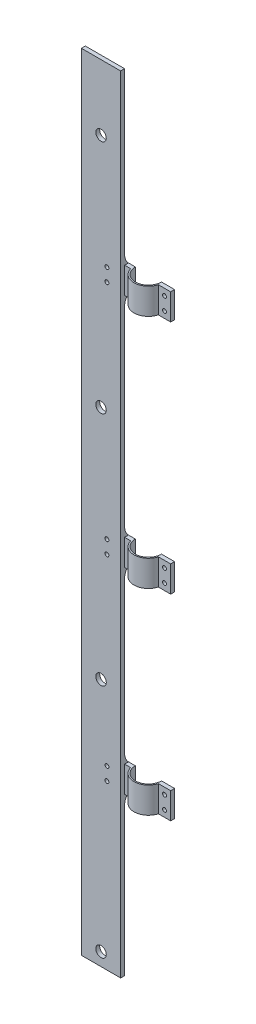
SolidWorks part; units mm, degrees
ref_plane "前视基准面" through (0, 0, 0) normal (0, 0, 1) x (1, 0, 0)
ref_plane "上视基准面" through (0, 0, 0) normal (0, 1, 0) x (1, 0, 0)
ref_plane "右视基准面" through (0, 0, 0) normal (1, 0, 0) x (0, 0, -1)
sketch "草图1" plane through (0, 0, 0) normal (0, 0, 1) x (1, 0, 0)
  line L0 (0, 0) -> (-30, 0)
  line L8 (-30, -300) -> (0, -300)
  line L9 (0, -300) -> (0, 300)
  line L10 (0, 300) -> (-30, 300)
  line L11 (-30, 300) -> (-30, -300)
  circle A6 centre (-15, 249.9934) radius 4
  circle A8 centre (-15, -290.0066) radius 4
  circle A10 centre (-15, -110.0066) radius 4
  circle A12 centre (-15, 69.9934) radius 4
extrude "凸台-拉伸1" add sketch "草图1" along normal blind 3 contours L10 L11 L0 L9 A12 A6 | L0 L11 L8 L9 A10 A8 region at (-15, -149.4351, 0) region at (-15, 149.8871, 0)
sketch "草图3" plane through (0, 0, 0) normal (0, 0, -1) x (-1, 0, 0)
  line L0 (15, 249.9934) -> (15, 159.9934)
  line L1 (15, 69.9934) -> (15, -20.0066)
  line L2 (15, -110.0066) -> (15, -170.0066)
ref_plane "基准面1" through (0, -20.0066, 0) normal (0, 1, 0) x (1, 0, 0)
ref_plane "基准面2" through (0, -170.0066, 0) normal (0, 1, 0) x (1, 0, 0)
ref_plane "基准面3" through (0, 159.9934, 0) normal (0, 1, 0) x (1, 0, 0)
sketch "草图10" plane through (0, -20.0066, 0) normal (0, 1, 0) x (1, 0, 0)
  line L0 (-30, 0) -> (4.617, 0)
  line L1 (-30, 3) -> (5.2, 3)
  line L2 (-30, 3) -> (-30, 0)
  line L4 (35.2, 3) -> (35.2, 0)
  line L7 (35.2, 0) -> (25.783, 0)
  line L10 (25.2, 3) -> (35.2, 3)
  arc A2 (25.783, 0) -> (4.617, 0) centre (15.2, 3) cw
  arc A3 (25.2, 3) -> (5.2, 3) centre (15.2, 3) cw
extrude "凸台-拉伸2" add sketch "草图10" along normal mid plane 20
sketch "草图11" plane through (0, 159.9934, 0) normal (0, 1, 0) x (1, 0, 0)
  line L0 (-30, 0) -> (4.617, 0)
  line L1 (-30, 3) -> (5.2, 3)
  line L2 (-30, 3) -> (-30, 0)
  line L3 (35.2, 3) -> (35.2, 0)
  line L4 (35.2, 0) -> (25.783, 0)
  line L5 (25.2, 3) -> (35.2, 3)
  arc A0 (25.783, 0) -> (4.617, 0) centre (15.2, 3) cw
  arc A1 (25.2, 3) -> (5.2, 3) centre (15.2, 3) cw
extrude "凸台-拉伸3" add sketch "草图11" along normal mid plane 20
sketch "草图12" plane through (0, -170.0066, 0) normal (0, 1, 0) x (1, 0, 0)
  line L0 (-30, 0) -> (4.617, 0)
  line L4 (-30, 3) -> (5.2, 3)
  line L5 (-30, 3) -> (-30, 0)
  line L6 (35.2, 3) -> (35.2, 0)
  line L8 (35.2, 0) -> (25.783, 0)
  line L9 (25.2, 3) -> (35.2, 3)
  arc A0 (25.783, 0) -> (4.617, 0) centre (15.2, 3) cw
  arc A1 (25.2, 3) -> (5.2, 3) centre (15.2, 3) cw
extrude "凸台-拉伸4" add sketch "草图12" along normal mid plane 20
sketch "草图13" plane through (0, 0, 3) normal (0, 0, 1) x (1, 0, 0)
  circle A0 centre (30.4915, 164.9934) radius 1.5
  circle A1 centre (30.4915, 154.9934) radius 1.5
  circle A2 centre (-10.5, 154.9934) radius 1.5
  circle A3 centre (-10.5, 164.9934) radius 1.5
  circle A4 centre (30.4915, -15.0066) radius 1.5
  circle A5 centre (30.4915, -25.0066) radius 1.5
  circle A6 centre (-10.5, -25.0066) radius 1.5
  circle A7 centre (-10.5, -15.0066) radius 1.5
  circle A8 centre (30.4915, -165.0066) radius 1.5
  circle A9 centre (30.4915, -175.0066) radius 1.5
  circle A10 centre (-10.5, -175.0066) radius 1.5
  circle A11 centre (-10.5, -165.0066) radius 1.5
extrude "切除-拉伸1" cut sketch "草图13" against normal blind 20
fillet "圆角1" radius 10 6 edges at (-15, -160.0066, 0) (-15, -180.0066, 0) (-15, -30.0066, 0) (-15, -10.0066, 0) (-15, 149.9934, 0) (-15, 169.9934, 0)
